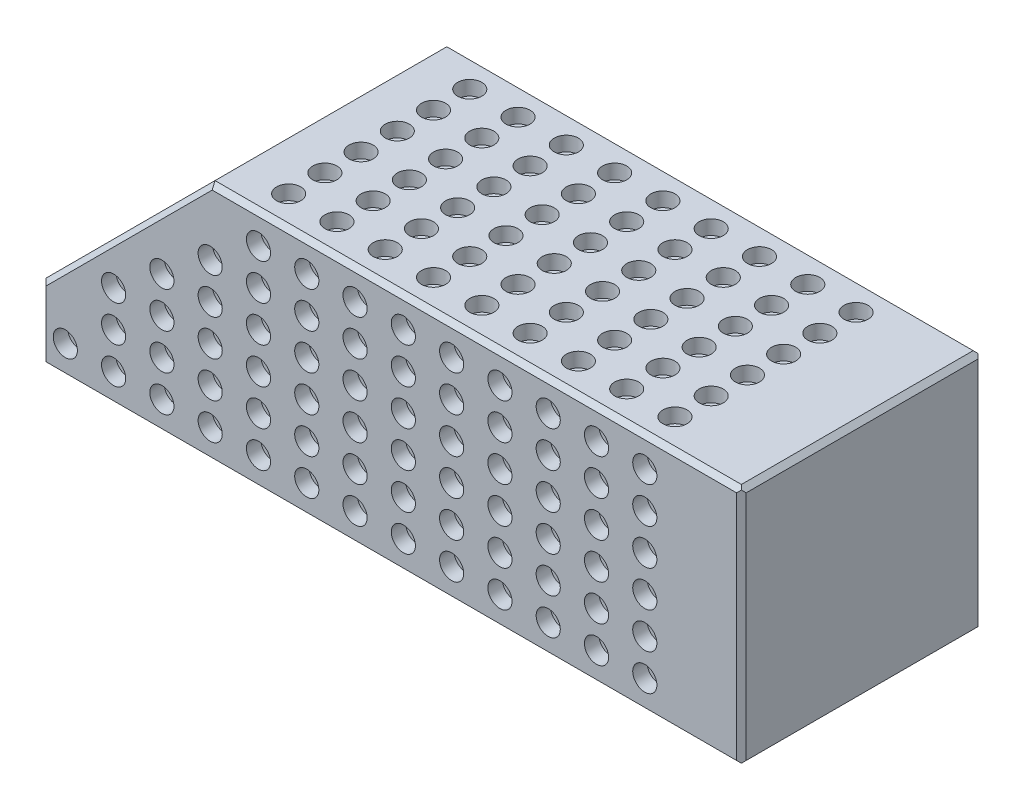
SolidWorks part; units mm, degrees
material "K110"
ref_plane "Front Plane" through (0, 0, 0) normal (0, 0, 1) x (1, 0, 0)
ref_plane "Top Plane" through (0, 0, 0) normal (0, 1, 0) x (1, 0, 0)
ref_plane "Right Plane" through (0, 0, 0) normal (1, 0, 0) x (0, 0, -1)
sketch "Sketch1" plane through (0, 0, 0) normal (0, 0, 1) x (1, 0, 0)
  line L1 (-72.5, -25) -> (72.5, -25)
  line L2 (-72.5, -25) -> (-72.5, 25)
  line L3 (-72.5, 25) -> (72.5, 25)
  line L4 (72.5, -25) -> (72.5, 25)
  line L5 (-72.5, -25) -> (72.5, 25) construction
  line L6 (-72.5, 25) -> (72.5, -25) construction
  point P0 (0, 0)
  dimension "D1" = 50
  dimension "D2" = 145
extrude "Boss-Extrude1" add sketch "Sketch1" along normal mid plane 50
sketch "Sketch2" plane through (0, 0, 0) normal (0, 0, 1) x (1, 0, 0)
  line L0 (-72.5, -10) -> (-37.5, 25)
  line L1 (-72.5, 25) -> (-72.5, -25) construction
  line L2 (72.5, 25) -> (-72.5, 25) construction
  line L3 (-37.5, 25) -> (-72.5, 25)
  line L4 (-72.5, 25) -> (-72.5, -10)
  dimension "D1" = 45
  dimension "D2" = 35
extrude "Cut-Extrude1" cut sketch "Sketch2" against normal through all both and the other way through all
hole_wizard "Ø12.0 (12) Diameter Hole1" positions "Sketch9" profile "Sketch4" hole size "Ø12.0" standard "ISO"
sketch "Sketch9" plane through (-72.5, 0, 0) normal (-1, 0, 0) x (0, 0, 1)
  line L0 (25, -25) -> (-25, -25) construction
  point P0 (0, -5)
  dimension "D1" = 20
sketch "Sketch4" plane through (-72.5, -5, 0) normal (0, 1, 0) x (0, 0, 1)
  line L0 (0, 0) -> (0, 20.5)
  line L1 (0, 20.5) -> (6, 20.5)
  line L2 (6, 20.5) -> (6, 0)
  line L5 (6, 0) -> (0, 0)
  line L10 (0, 20.5) -> (-6, 20.5) construction
  line L11 (0, -6.35) -> (0, 107.95) construction
  dimension "Hole Dia." = 12
  dimension "Hole Depth" = 20.5
  dimension "Drill Angle" = 180
hole_wizard "M10 Tapped Hole2" positions "Sketch12" profile "Sketch11" tap size "M10" standard "ISO"
sketch "Sketch12" plane through (-52, 0, 0) normal (-1, 0, 0) x (0, 0, 1)
  point P0 (0, -5)
sketch "Sketch11" plane through (-52, -5, 0) normal (0, 1, 0) x (0, 0, 1)
  line L0 (0, 0) -> (0, 27.5)
  line L1 (0, 27.5) -> (4.25, 24.9463)
  line L2 (4.25, 24.9463) -> (4.25, 0)
  line L5 (4.25, 0) -> (0, 0)
  line L10 (0, 27.5) -> (-4.25, 24.9463) construction
  line L11 (0, -6.35) -> (0, 107.95) construction
  dimension "Tap Drill Dia." = 8.5
  dimension "Tap Drill Depth" = 27.5
  dimension "Drill Angle" = 118
cosmetic thread "Hole Thread3" parameters "D1"=20, "D2"=10
chamfer "Chamfer1" distance 1 angle 45 10 edges at (-72.5, -17.5, -25) (0, -25, -25) (72.5, 0, -25) (17.5, 25, -25) (-55, 7.5, -25) (72.5, 0, 25) (0, -25, 25) (-72.5, -17.5, 25) (-55, 7.5, 25) (17.5, 25, 25)
chamfer "Chamfer2" distance 1 angle 45 2 edges at (72.5, -25, 0) (72.5, 25, 0)
chamfer "Chamfer3" distance 1 angle 45 1 edges at (-72.5, -25, 0)
sketch "Sketch13" plane through (0, -25, 0) normal (0, -1, 0) x (1, 0, 0)
  line L0 (71.5, -25) -> (-71.5, -25) construction
  line L1 (-72.5, -24) -> (-72.5, 24) construction
  circle A0 centre (-66.25, -18.75) radius 2.5
  dimension "D1" = 5
  dimension "D2" = 6.25
  dimension "D3" = 6.25
extrude "Cut-Extrude2" cut sketch "Sketch13" against normal blind 3
pattern_linear "LPattern1" count 6 spacing 7.5 along (0, 0, 1) count 13 spacing 10 along (1, 0, 0) of "Cut-Extrude2"
sketch "Sketch14" plane through (0, 0, 25) normal (0, 0, 1) x (1, 0, 0)
  line L0 (72.5, 24) -> (72.5, -24) construction
  line L1 (-37.5, 25) -> (71.5, 25) construction
  circle A0 centre (52.5, 18.75) radius 2.5
  dimension "D1" = 5
  dimension "D2" = 20
  dimension "D3" = 6.25
extrude "Cut-Extrude3" cut sketch "Sketch14" against normal blind 3
pattern_linear "LPattern2" count 6 spacing 7.5 along (0, -1, 0) count 13 spacing 10 along (-1, 0, 0) skipping (0, 9), (0, 10), (0, 11), (0, 12), (1, 10), (1, 11), (1, 12), (2, 11), (2, 12), (3, 12), (4, 12) of "Cut-Extrude3"
sketch "Sketch15" plane through (0, 25, 0) normal (0, 1, 0) x (1, 0, 0)
  line L0 (72.5, 24) -> (72.5, -24) construction
  line L1 (-37.0858, 25) -> (71.5, 25) construction
  circle A0 centre (52.5, 18.75) radius 2.5
  dimension "D1" = 5
  dimension "D2" = 20
  dimension "D3" = 6.25
extrude "Cut-Extrude4" cut sketch "Sketch15" against normal blind 3
pattern_linear "LPattern3" count 6 spacing 7.5 along (0, 0, 1) count 9 spacing 10 along (-1, 0, 0) of "Cut-Extrude4"
sketch "Sketch16" plane through (0, 0, -25) normal (0, 0, -1) x (-1, 0, 0)
  line L0 (-72.5, -24) -> (-72.5, 24) construction
  line L1 (-71.5, 25) -> (37.5, 25) construction
  circle A0 centre (-52.5, 18.75) radius 2.5
  dimension "D1" = 5
  dimension "D2" = 20
  dimension "D3" = 6.25
extrude "Cut-Extrude5" cut sketch "Sketch16" against normal blind 3
pattern_linear "LPattern4" count 13 spacing 10 along (-1, 0, 0) count 6 spacing 7.5 along (0, -1, 0) skipping (9, 0), (10, 0), (10, 1), (11, 0), (11, 1), (11, 2), (12, 0), (12, 1), (12, 2), (12, 3), (12, 4) of "Cut-Extrude5"
sketch "Sketch17" plane through (-31.25, 31.25, 0) normal (-0.7071, 0.7071, 0) x (0, 0, 1)
  line L0 (-25, -57.9221) -> (-25, -9.253) construction
  line L1 (-24, -8.8388) -> (24, -8.8388) construction
  circle A0 centre (-18.75, -16.3388) radius 2.5
  dimension "D1" = 5
  dimension "D2" = 6.25
  dimension "D3" = 7.5
extrude "Cut-Extrude6" cut sketch "Sketch17" against normal blind 3
pattern_linear "LPattern5" count 6 spacing 7.5 along (0, 0, 1) count 6 spacing 7.5 along (-0.7071, -0.7071, 0) skipping (2, 0), (2, 1), (2, 2), (2, 3), (2, 4), (2, 5), (3, 0), (3, 1), (3, 2), (3, 3), (3, 4), (3, 5) of "Cut-Extrude6"
sketch "Sketch18" [suppressed] plane through (-31.25, 31.25, 0) normal (-0.7071, 0.7071, 0) x (0, 0, 1)
  line L0 (-24, -33.5876) -> (24, -33.5876)
  line L1 (-24, -8.8388) -> (-24, -58.3363) construction
  line L2 (24, -58.3363) -> (24, -8.8388) construction
  line L3 (0, -8.8388) -> (0, -33.5876)
  line L4 (-24, -8.8388) -> (24, -8.8388) construction
